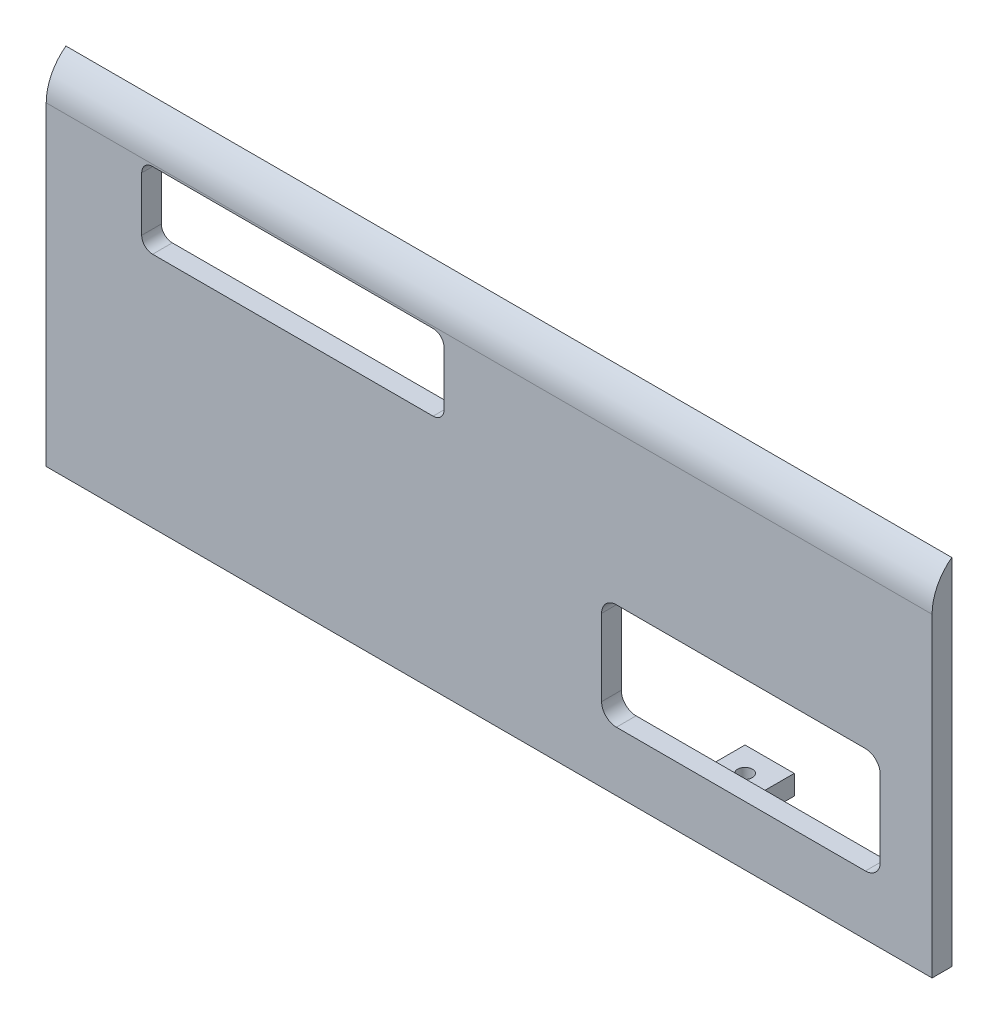
SolidWorks part; units mm, degrees
ref_plane "Alzado" through (0, 0, 0) normal (0, 0, 1) x (1, 0, 0)
ref_plane "Planta" through (0, 0, 0) normal (0, 1, 0) x (1, 0, 0)
ref_plane "Vista lateral" through (0, 0, 0) normal (1, 0, 0) x (0, 0, -1)
sketch "Croquis1" plane through (0, 0, 0) normal (0, 0, 1) x (1, 0, 0)
  line L1 (-98, 60) -> (-98, -4)
  line L2 (90, 60) -> (90, -4)
  line L3 (86, 68) -> (-94, 68) construction
  line L5 (86, -4) -> (-94, -4) construction
  line L9 (86, 68) -> (-94, 68)
  line L11 (90, -4) -> (-98, -4)
  arc A4 (90, 60) -> (86, 68) centre (80, 60) ccw construction
  arc A5 (90, 60) -> (86, 68) centre (80, 60) ccw
  arc A6 (-94, 68) -> (-98, 60) centre (-88, 60) ccw construction
  arc A7 (-94, 68) -> (-98, 60) centre (-88, 60) ccw
extrude "Saliente-Extruir1" add sketch "Croquis1" along normal blind 4
sketch "Croquis2" plane through (0, 0, 0) normal (0, 0, -1) x (-1, 0, 0)
  line L0 (4, 0) -> (4, 68) construction
  line L1 (-86, 0) -> (94, 0) construction
  line L2 (-86, 68) -> (94, 68) construction
  line L3 (-82, 0) -> (4, 0) construction
  line L4 (-39, 0) -> (-38.7, 71) construction
  line L5 (41.9915, 0) -> (41.9915, 4)
  line L6 (-33.9915, 0) -> (-43.9915, 0)
  line L7 (-33.9915, 0) -> (-33.9915, 4)
  line L8 (-33.9915, 4) -> (-43.9915, 4)
  line L9 (-43.9915, 0) -> (-43.9915, 4)
  line L10 (-33.9915, 0) -> (-43.9915, 4) construction
  line L11 (-33.9915, 4) -> (-43.9915, 0) construction
  line L12 (41.9915, 0) -> (51.9915, 0)
  line L13 (51.9915, 0) -> (51.9915, 4)
  line L14 (41.9915, 4) -> (51.9915, 4)
  point P15 (-38.9915, 2)
  dimension "D1" = 4
  dimension "D2" = 10
extrude "Saliente-Extruir2" add sketch "Croquis2" along normal blind 10
sketch "Croquis3" plane through (0, 0, 0) normal (0, -1, 0) x (1, 0, 0)
  line L1 (-41.9915, 0) -> (-51.9915, 0)
  line L2 (-41.9915, 0) -> (-41.9915, -10)
  line L3 (-41.9915, -10) -> (-51.9915, -10)
  line L4 (-51.9915, 0) -> (-51.9915, -10)
  line L5 (-41.9915, 0) -> (-51.9915, -10) construction
  line L6 (-41.9915, -10) -> (-51.9915, 0) construction
  line L7 (-44.2415, -3.4123) -> (-46.9915, -1.8246)
  line L8 (-46.9915, -1.8246) -> (-49.7415, -3.4123)
  line L9 (-49.7415, -3.4123) -> (-49.7415, -6.5877)
  line L10 (-49.7415, -6.5877) -> (-46.9915, -8.1754)
  line L11 (-46.9915, -8.1754) -> (-44.2415, -6.5877)
  line L12 (-44.2415, -6.5877) -> (-44.2415, -3.4123)
  line L13 (43.9915, 0) -> (33.9915, 0)
  line L14 (43.9915, 0) -> (43.9915, -10)
  line L15 (43.9915, -10) -> (33.9915, -10)
  line L16 (33.9915, 0) -> (33.9915, -10)
  line L17 (43.9915, 0) -> (33.9915, -10) construction
  line L18 (43.9915, -10) -> (33.9915, 0) construction
  line L19 (41.7415, -3.4123) -> (38.9915, -1.8246)
  line L20 (38.9915, -1.8246) -> (36.2415, -3.4123)
  line L21 (36.2415, -3.4123) -> (36.2415, -6.5877)
  line L22 (36.2415, -6.5877) -> (38.9915, -8.1754)
  line L23 (38.9915, -8.1754) -> (41.7415, -6.5877)
  line L24 (41.7415, -6.5877) -> (41.7415, -3.4123)
  circle A0 centre (-46.9915, -5) radius 1.5
  circle A1 centre (-46.9915, -5) radius 2.75 construction
  circle A2 centre (38.9915, -5) radius 1.5
  circle A3 centre (38.9915, -5) radius 2.75 construction
  point P4 (-46.9915, -5)
  point P20 (38.9915, -5)
  dimension "D1" = 5.5
  dimension "D2" = 3
  dimension "D4" = 3
  dimension "D3" = 5.5
extrude "Cortar-Extruir1" cut sketch "Croquis3" against normal blind 10 contours A2 | A0 region at (-46.9915, 0, -5) region at (38.9915, 0, -5)
extrude "Cortar-Extruir2" cut sketch "Croquis3<3>" against normal blind 1.65 contours L11 L12 L7 L8 L9 L10 A0 | L23 L24 L19 L20 L21 L22 A2 region at (-44.3256, 0, -5) region at (41.6575, 0, -5)
sketch "Croquis3<3>" plane through (0, 0, 0) normal (0, -1, 0) x (1, 0, 0) same geometry as "Croquis3"
fillet "Redondeo2" radius 10 1 edges at (-4, 68, 4)
sketch "Croquis4" plane through (0, 0, 0) normal (0, 0, -1) x (-1, 0, 0)
  line L0 (-39.4, 19.72) -> (-39.4, 21.62) construction
  line L1 (-39.4, 10.2574) -> (-39.4, 26.22) construction
  line L2 (-73.05, 13.9) -> (-57.55, 13.9) construction
  line L3 (-39.2, 10.0574) -> (-39.2, 26.42)
  line L4 (-41.3731, 10.2574) -> (-51.4269, 10.2574) construction
  line L5 (-53.4, 19.72) -> (-53.4, 21.62) construction
  line L6 (-53.4, 10.2574) -> (-53.4, 26.22) construction
  line L7 (-73.25, 13.9) -> (-57.35, 13.9) construction
  line L9 (-39.4, 10.2574) -> (-53.4, 10.2574) construction
  line L10 (-39.2, 26.42) -> (-53.6, 26.42)
  line L12 (-21.05, 17.6) -> (-21.05, 20.6) construction
  line L13 (-35.95, 17.6) -> (-35.95, 20.6) construction
  line L14 (-25.6423, 11.58) -> (-28.45, 11.58) construction
  line L15 (-21.05, 11.58) -> (-21.05, 27.4) construction
  line L16 (-35.95, 11.58) -> (-35.95, 27.4) construction
  line L17 (-21.05, 11.58) -> (-35.95, 11.58) construction
  line L18 (-53.6, 10.0574) -> (-53.6, 26.42)
  line L19 (-39.2, 10.0574) -> (-53.6, 10.0574)
  line L20 (-73.45, 13.7) -> (-57.15, 13.7)
  line L21 (-57.15, 13.7) -> (-57.15, 27.6)
  line L22 (-57.15, 27.6) -> (-73.45, 27.6)
  line L23 (-67.83, 27.4) -> (-72.2, 27.4) construction
  line L24 (-73.45, 27.6) -> (-73.45, 13.7)
  line L25 (-20.85, 11.38) -> (-20.85, 27.6)
  line L26 (-36.15, 27.6) -> (-20.85, 27.6)
  line L27 (-36.15, 11.38) -> (-36.15, 27.6)
  line L28 (-57.35, 27.4) -> (-73.25, 27.4) construction
  line L30 (-73.25, 27.05) -> (-73.25, 14.1066) construction
  line L31 (-57.35, 14.1066) -> (-57.35, 27.05) construction
  line L32 (-73.25, 27.4) -> (-73.25, 13.9) construction
  line L33 (-57.35, 13.9) -> (-57.35, 27.4) construction
  line L34 (-20.85, 11.38) -> (-36.15, 11.38)
  line L35 (-41.99, 26.22) -> (-44.81, 26.22) construction
  line L38 (-30.09, 27.4) -> (-26.91, 27.4) construction
  line L40 (-39.4, 26.22) -> (-53.4, 26.22) construction
  line L44 (-35.95, 27.4) -> (-21.05, 27.4) construction
  dimension "D1" = 0.2
extrude "Cortar-Extruir4" cut sketch "Croquis4" against normal up to next
sketch "Croquis5" plane through (0, 0, 4) normal (0, 0, 1) x (1, 0, 0)
  line L0 (20.85, 11.38) -> (20.85, 27.6) construction
  line L1 (75.45, 8.0574) -> (18.85, 8.0574)
  line L2 (75.45, 8.0574) -> (75.45, 29.6)
  line L3 (75.45, 29.6) -> (18.85, 29.6)
  line L4 (18.85, 8.0574) -> (18.85, 29.6)
  line L5 (75.45, 8.0574) -> (18.85, 29.6) construction
  line L6 (75.45, 29.6) -> (18.85, 8.0574) construction
  line L7 (53.6, 10.0574) -> (39.2, 10.0574) construction
  line L8 (20.85, 27.6) -> (36.15, 27.6) construction
  line L9 (73.45, 27.6) -> (73.45, 13.7) construction
  point P4 (47.15, 18.8287)
  dimension "D1" = 2
  dimension "D2" = 2
  dimension "D3" = 2
  dimension "D4" = 2
extrude "Cortar-Extruir5" cut sketch "Croquis5" against normal up to surface (4 mm away) up to face at (28.5, 19.49, 0)
fillet "Redondeo3" radius 3 4 edges at (75.45, 29.6, 2) (18.85, 29.6, 2) (18.85, 8.0574, 2) (75.45, 8.0574, 2)
sketch "Croquis6" plane through (0, 0, 4) normal (0, 0, 1) x (1, 0, 0)
  line L0 (-98, 60) -> (-98, -4) construction
  line L1 (-13.17, 44.17) -> (-74.6, 44.17)
  line L2 (-13.17, 44.17) -> (-13.17, 59.6)
  line L3 (-13.17, 59.6) -> (-74.6, 59.6)
  line L4 (-74.6, 44.17) -> (-74.6, 59.6)
  line L5 (-13.17, 44.17) -> (-74.6, 59.6) construction
  line L6 (-13.17, 59.6) -> (-74.6, 44.17) construction
  line L7 (90, 60) -> (-98, 60) construction
  point P4 (-43.885, 51.885)
  dimension "D1" = 15.43
  dimension "D2" = 61.43
  dimension "D3" = 23.4
  dimension "D4" = 0.4
extrude "Cortar-Extruir6" cut sketch "Croquis6" against normal up to surface (4 mm away) up to face at (47.15, 18.8287, 0)
fillet "Redondeo4" radius 2.22 4 edges at (-74.6, 59.6, 2) (-74.6, 44.17, 2) (-13.17, 59.6, 2) (-13.17, 44.17, 2)
sketch "Croquis8" plane through (0, 0, 4) normal (0, 0, 1) x (1, 0, 0)
  line L1 (86, 68) -> (90, 68)
  line L2 (86, 68) -> (86, -4)
  line L3 (86, -4) -> (90, -4)
  line L4 (90, 68) -> (90, -4)
  line L5 (86, 68) -> (90, -4) construction
  line L6 (86, -4) -> (90, 68) construction
  line L7 (-94, 68) -> (-98, 68)
  line L8 (-94, 68) -> (-94, -4)
  line L9 (-94, -4) -> (-98, -4)
  line L10 (-98, 68) -> (-98, -4)
  line L11 (-94, 68) -> (-98, -4) construction
  line L12 (-94, -4) -> (-98, 68) construction
  point P4 (88, 32)
  point P11 (-96, 32)
extrude "Cortar-Extruir7" cut sketch "Croquis8" against normal up to surface (4 mm away) up to face at (-43.885, 51.885, 0)
